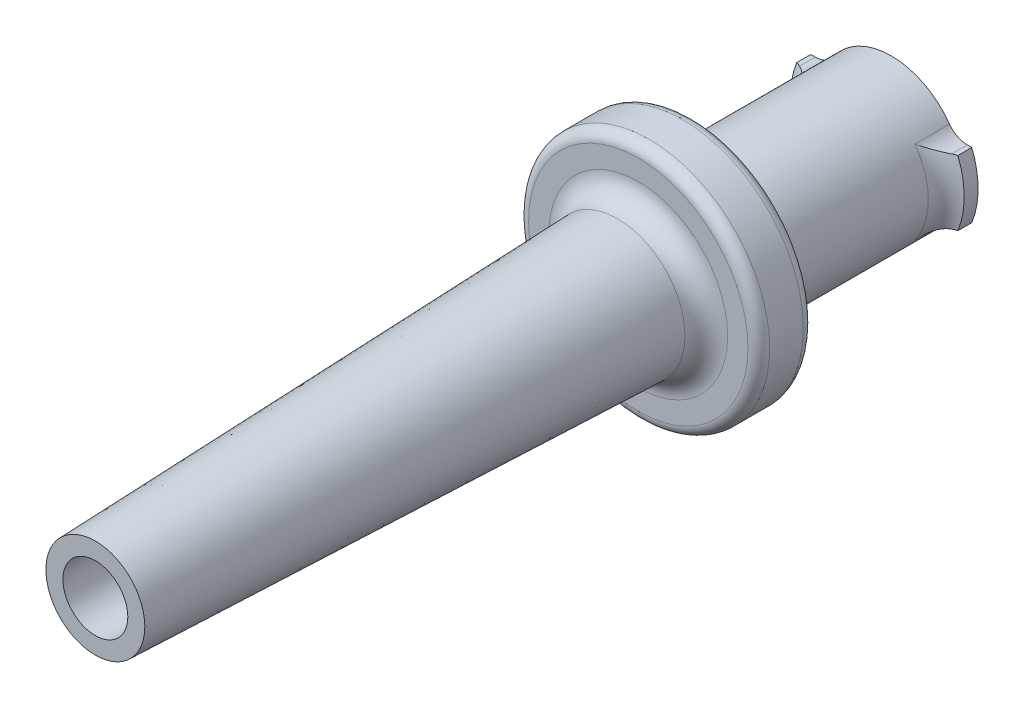
SolidWorks part; units mm, degrees
ref_plane "Front Plane" through (0, 0, 0) normal (0, 0, 1) x (1, 0, 0)
ref_plane "Top Plane" through (0, 0, 0) normal (0, 1, 0) x (1, 0, 0)
ref_plane "Right Plane" through (0, 0, 0) normal (1, 0, 0) x (0, 0, -1)
sketch "Sketch1" plane through (0, 0, 0) normal (0, 0, 1) x (1, 0, 0)
  line L1 (4, 1.5) -> (-4, 1.5)
  line L2 (4, 1.5) -> (4, -1.5)
  line L3 (4, -1.5) -> (-4, -1.5)
  line L4 (-4, 1.5) -> (-4, -1.5)
  circle A0 centre (0, 0) radius 4
  dimension "D1" = 4
  dimension "D2" = 4
  dimension "D3" = 1.5
  dimension "D4" = 3
extrude "Boss-Extrude1" add sketch "Sketch1" along normal blind 0.64 contours L1 A0 L3 region at (0, 0, 0)
sketch "Sketch2" plane through (0, 0, 0) normal (0, 0, -1) x (-1, 0, 0)
  circle A1 centre (0, 0) radius 3.3
extrude "Boss-Extrude2" add sketch "Sketch2" against normal blind 9.1
sketch "Sketch3" plane through (0, 0, 0) normal (0, 0, -1) x (-1, 0, 0)
  circle A0 centre (0, 0) radius 2.13
extrude "Cut-Extrude2" cut sketch "Sketch3" against normal blind 9.1 draft 4
sketch "Sketch4" plane through (0, 0, 9.1) normal (0, 0, 1) x (1, 0, 0)
  circle A0 centre (0, 0) radius 1.4937
  circle A1 centre (0, 0) radius 5.55
extrude "Boss-Extrude3" add sketch "Sketch4" along normal blind 2.55
sketch "Sketch8" plane through (0, 0, 11.65) normal (0, 0, 1) x (1, 0, 0)
  circle A0 centre (0, 0) radius 1.4937
  dimension "D1" = 2.9873
extrude "Boss-Extrude5" add sketch "Sketch8" along normal blind 25 separate body
sketch "Sketch9" plane through (0, 0, 11.65) normal (0, 0, 1) x (1, 0, 0)
  circle A0 centre (0, 0) radius 3.15
extrude "Boss-Extrude6" add sketch "Sketch9" along normal blind 25 draft 2
sketch "Sketch11" plane through (0, 0, 36.65) normal (0, 0, 1) x (1, 0, 0)
  circle A0 centre (0, 0) radius 1.495
extrude "Cut-Extrude7" cut sketch "Sketch11" against normal blind 25
fillet "Fillet6" radius 1 1 edges at (3.3, 0, 0.64)
fillet "Fillet7" radius 1 1 edges at (-3.3, 0, 0.64)
fillet "Fillet8" radius 1 4 edges at (-2.9394, -1.5, 0.797) (2.9394, -1.5, 0.797) (2.9394, 1.5, 0.797) (-2.9394, 1.5, 0.797)
fillet "Fillet9" radius 1 1 edges at (3.3, 0, 9.1)
fillet "Fillet10" radius 1 1 edges at (3.15, 0, 11.65)
fillet "Fillet11" radius 0.5 2 edges at (5.55, 0, 11.65) (5.55, 0, 9.1)
